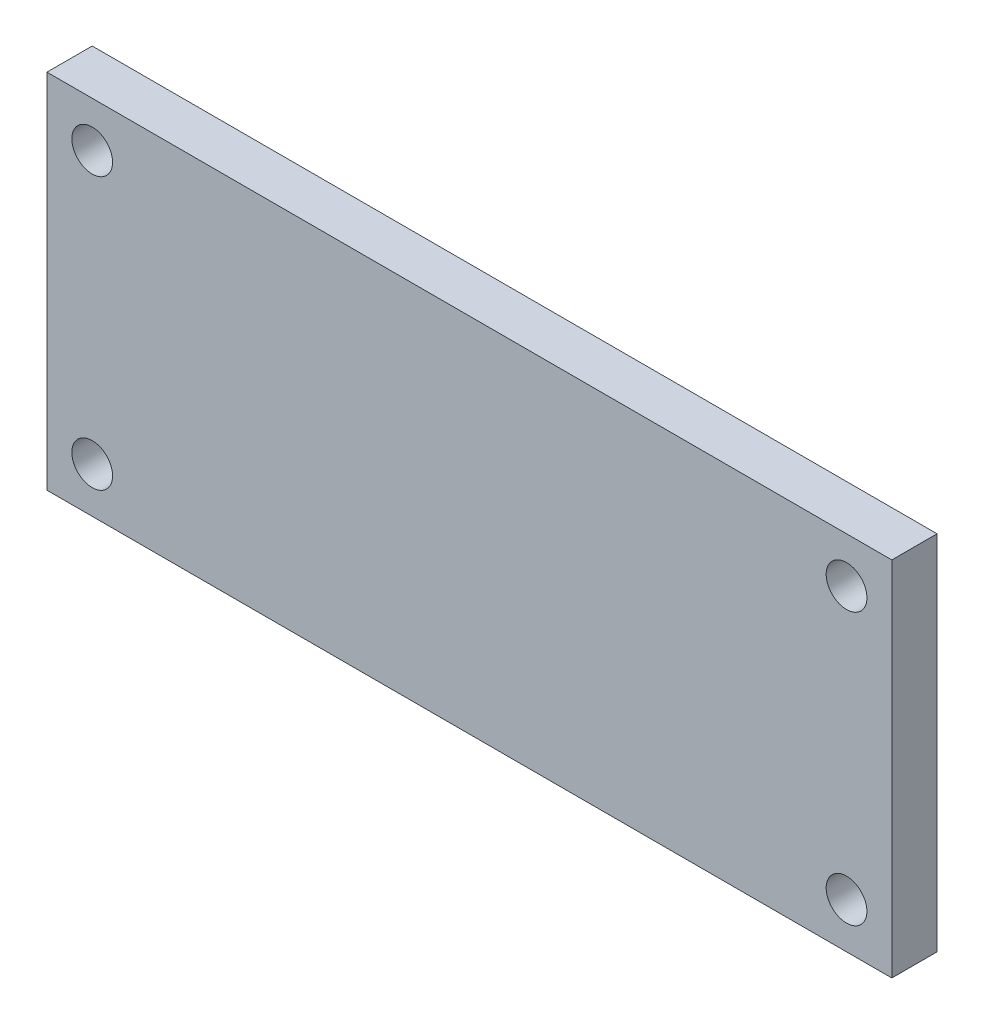
SolidWorks part; units mm, degrees
ref_plane "Front Plane" through (0, 0, 0) normal (0, 0, 1) x (1, 0, 0)
ref_plane "Top Plane" through (0, 0, 0) normal (0, 1, 0) x (1, 0, 0)
ref_plane "Right Plane" through (0, 0, 0) normal (1, 0, 0) x (0, 0, -1)
sketch "Sketch1" plane through (0, 0, 0) normal (0, 0, 1) x (1, 0, 0)
  line L1 (-140, -60) -> (140, -60)
  line L2 (-140, -60) -> (-140, 60)
  line L3 (-140, 60) -> (140, 60)
  line L4 (140, -60) -> (140, 60)
  circle A0 centre (-125, 45) radius 4.25
  circle A1 centre (125, 45) radius 4.25
  circle A2 centre (125, -45) radius 4.25
  circle A3 centre (-125, -45) radius 4.25
  point P0 (0, 0)
  dimension "D1" = 2
  dimension "D2" = 2
extrude "Boss-Extrude1" add sketch "Sketch1" along normal blind 15
sketch "Sketch2" plane through (0, 0, 15) normal (0, 0, 1) x (1, 0, 0)
  circle A0 centre (-125, 45) radius 6.75
  circle A1 centre (125, 45) radius 6.75
  circle A2 centre (125, -45) radius 6.75
  circle A3 centre (-125, -45) radius 6.75
  dimension "D1" = 2
  dimension "D2" = 2
extrude "Cut-Extrude1" cut sketch "Sketch2" against normal blind 10
chamfer "Chamfer2" distance 3 angle 45 1 edges at (-120.75, 45, 5)
chamfer "Chamfer3" distance 3 angle 45 3 edges at (129.25, 45, 5) (129.25, -45, 5) (-120.75, -45, 5)
